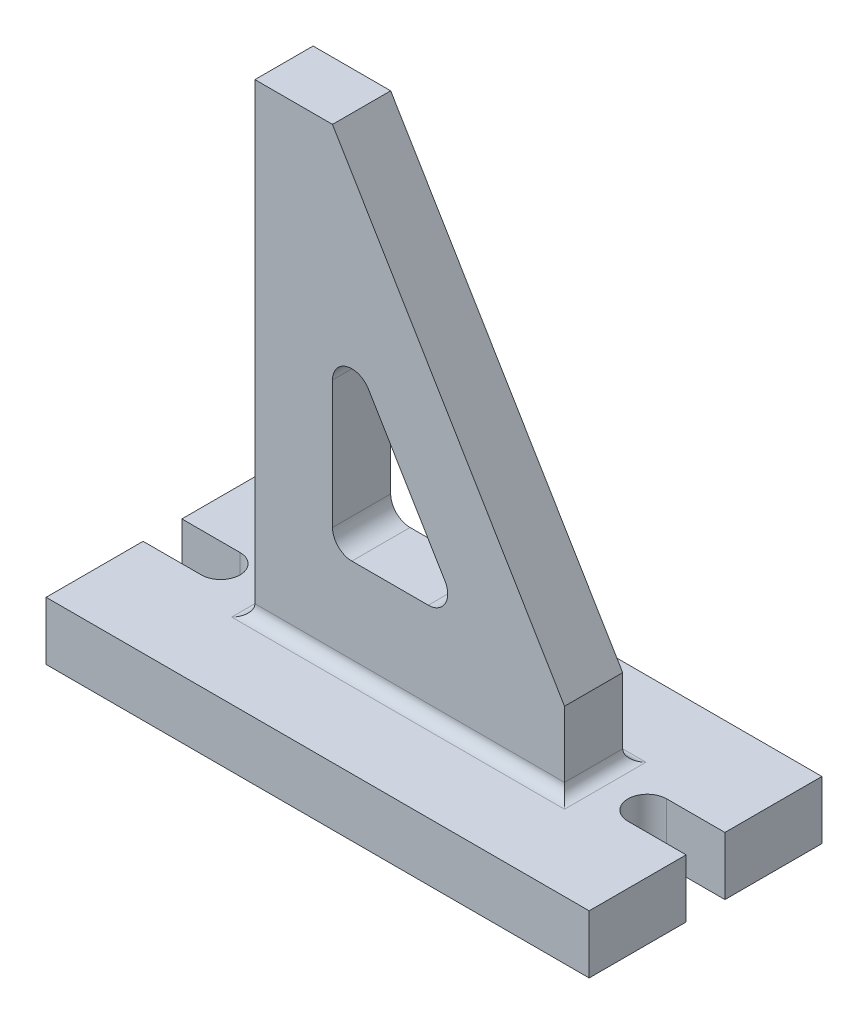
SolidWorks part; units mm, degrees
ref_plane "Front Plane" through (0, 0, 0) normal (0, 0, 1) x (1, 0, 0)
ref_plane "Top Plane" through (0, 0, 0) normal (0, 1, 0) x (1, 0, 0)
ref_plane "Right Plane" through (0, 0, 0) normal (1, 0, 0) x (0, 0, -1)
sketch "Sketch1" plane through (0, 0, 0) normal (0, 1, 0) x (1, 0, 0)
  line L1 (-76.2, 38.1) -> (101.6, 38.1)
  line L2 (-76.2, 38.1) -> (-76.2, -38.1)
  line L3 (-76.2, -38.1) -> (101.6, -38.1)
  line L4 (101.6, 38.1) -> (101.6, -38.1)
  dimension "D1" = 76.2
  dimension "D2" = 177.8
  dimension "D3" = 76.2
  dimension "D4" = 38.1
extrude "Milling Support Base" add sketch "Sketch1" against normal blind 19.05
sketch "Sketch2" plane through (0, 0, 0) normal (0, 1, 0) x (1, 0, 0)
  line L0 (-76.2, 38.1) -> (-76.2, -38.1) construction
  line L2 (-76.2, 6.35) -> (-57.15, 6.35)
  line L4 (-76.2, 6.35) -> (-76.2, -6.35)
  line L5 (-76.2, -6.35) -> (-57.15, -6.35)
  line L7 (-76.2, -38.1) -> (101.6, -38.1) construction
  arc A0 (-57.15, 6.35) -> (-57.15, -6.35) centre (-57.15, 0) cw
  dimension "D3" = 19.05
  dimension "D1" = 38.1
  dimension "D2" = 6.35
extrude "Bolt Slot Left End" cut sketch "Sketch2" against normal through all
sketch "Sketch3" plane through (0, -19.05, 0) normal (0, -1, 0) x (1, 0, 0)
  line L0 (101.6, 38.1) -> (101.6, -38.1) construction
  line L1 (101.6, 6.35) -> (82.55, 6.35)
  line L2 (101.6, 6.35) -> (101.6, -6.35)
  line L3 (101.6, -6.35) -> (82.55, -6.35)
  line L5 (101.6, -38.1) -> (-76.2, -38.1) construction
  arc A0 (82.55, 6.35) -> (82.55, -6.35) centre (82.55, 0) ccw
  dimension "D1" = 19.05
  dimension "D2" = 12.7
  dimension "D3" = 38.1
extrude "Bolt Slot Right End" cut sketch "Sketch3" against normal through all
sketch "Sketch4" plane through (0, 0, 0) normal (0, 0, 1) x (1, 0, 0)
  line L0 (-36.4086, 0) -> (-36.4086, 152.4)
  line L1 (-76.2, 0) -> (101.6, 0) construction
  line L2 (-36.4086, 152.4) -> (-11.0086, 152.4)
  line L3 (64.9592, 0) -> (64.9592, 25.4)
  line L4 (64.9592, 25.4) -> (-11.0086, 152.4)
  line L5 (64.9592, 0) -> (-36.4086, 0)
  dimension "D1" = 152.4
  dimension "D2" = 25.4
  dimension "D3" = 25.4
extrude "Outer Triangle" add sketch "Sketch4" along normal mid plane 19.05
sketch "Sketch5" plane through (0, 0, 9.525) normal (0, 0, 1) x (1, 0, 0)
  line L0 (-4.6586, 31.75) -> (20.3657, 31.75)
  line L1 (25.8152, 41.3597) -> (0.7909, 83.1944)
  line L2 (-11.0086, 79.9347) -> (-11.0086, 38.1)
  line L3 (-36.4086, 0) -> (64.9592, 0) construction
  line L5 (-36.4086, 152.4) -> (-36.4086, 0) construction
  line L6 (64.9592, 25.4) -> (-11.0086, 152.4) construction
  arc A0 (25.8152, 41.3597) -> (20.3657, 31.75) centre (20.3657, 38.1) cw
  arc A1 (-4.6586, 31.75) -> (-11.0086, 38.1) centre (-4.6586, 38.1) cw
  arc A2 (0.7909, 83.1944) -> (-11.0086, 79.9347) centre (-4.6586, 79.9347) ccw
  dimension "D4" = 6.35
  dimension "D1" = 31.75
  dimension "D2" = 25.4
  dimension "D3" = 25.4
extrude "Inner Triangle" cut sketch "Sketch5" against normal through all
ref_plane "Plane1" through (-41.4886, 0, 0) normal (-1, 0, 0) x (0, 0, 1)
sketch "Sketch6" plane through (-41.4886, 0, 0) normal (-1, 0, 0) x (0, 0, 1)
  line L0 (9.525, 152.4) -> (9.525, 0) construction
  line L1 (-9.525, 152.4) -> (9.525, 152.4)
  line L2 (-9.525, 152.4) -> (-9.525, 76.2)
  line L3 (-9.525, 76.2) -> (9.525, 76.2)
  line L4 (9.525, 152.4) -> (9.525, 76.2)
  dimension "D1" = 76.2
split line "Split Line1"
fillet "Fillet at Triangle base" radius 3.81 4 edges at (14.2753, 0, -9.525) (64.9592, 0, 0) (14.2753, 0, 9.525) (-36.4086, 0, 0)
